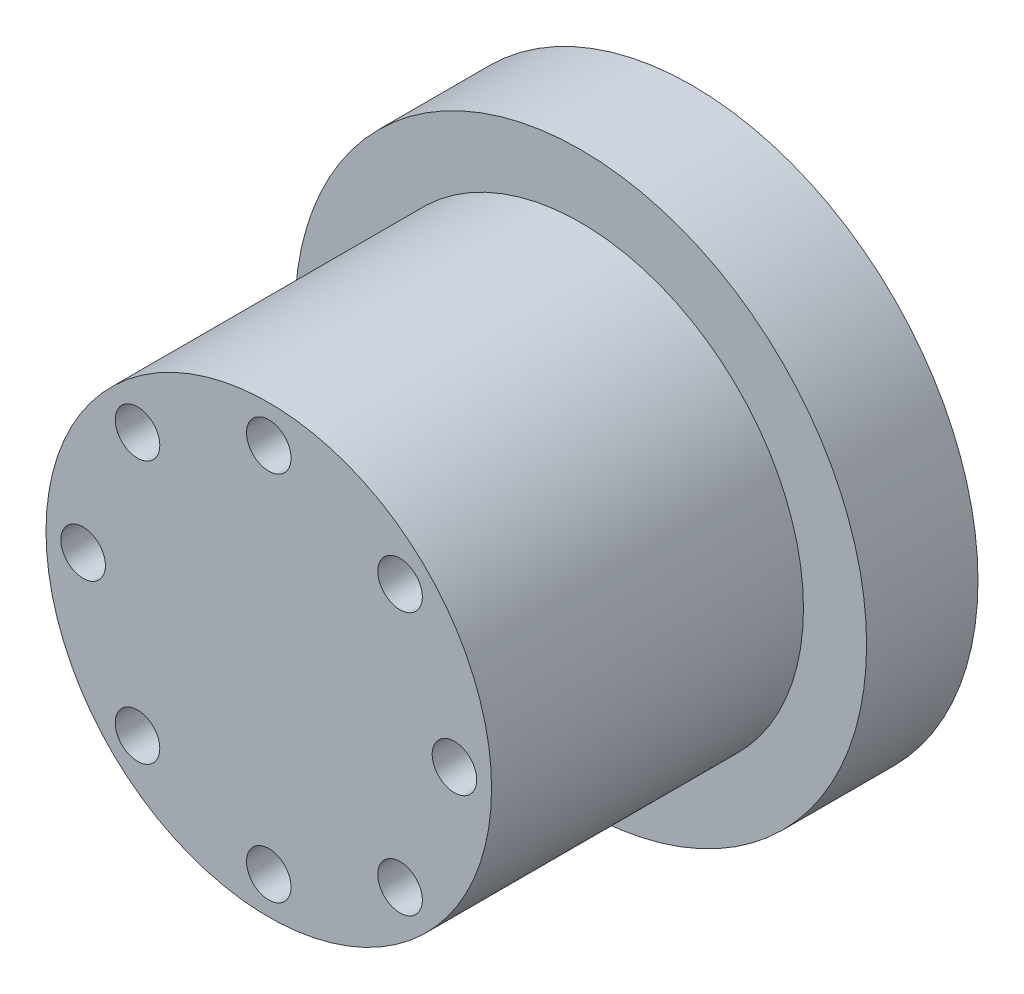
SolidWorks part; units mm, degrees
ref_plane "Front Plane" through (0, 0, 0) normal (0, 0, 1) x (1, 0, 0)
ref_plane "Top Plane" through (0, 0, 0) normal (0, 1, 0) x (1, 0, 0)
ref_plane "Right Plane" through (0, 0, 0) normal (1, 0, 0) x (0, 0, -1)
sketch "Sketch2" plane through (0, 0, 0) normal (0, 0, 1) x (1, 0, 0)
  circle A0 centre (0, 0) radius 30
  circle A3 centre (0, 0) radius 38.5
  dimension "D1" = 60
  dimension "D2" = 77
extrude "Boss-Extrude1" add sketch "Sketch2" along normal blind 42 contours A0
extrude "Boss-Extrude2" add sketch "Sketch2<4>" against normal blind 15 contours A0 | A0 region at (0, 0, 0) region at (-37.4111, 0, 0)
sketch "Sketch2<4>" plane through (0, 0, 0) normal (0, 0, 1) x (1, 0, 0) same geometry as "Sketch2"
sketch "Sketch3" plane through (0, 0, -15) normal (0, 0, -1) x (-1, 0, 0)
  circle A1 centre (0, 25) radius 3
  circle A2 centre (25, 0) radius 3
  circle A3 centre (0, -25) radius 3
  circle A4 centre (-25, 0) radius 3
  circle A5 centre (0, 0) radius 25 construction
  point P14 (0, 0)
  dimension "D1" = 4
  dimension "D2" = 6
  dimension "D3" = 50
extrude "Cut-Extrude1" cut sketch "Sketch3" against normal blind 10
sketch "Sketch4" plane through (0, 0, 42) normal (0, 0, 1) x (1, 0, 0)
  circle A1 centre (0, 25) radius 3
  circle A2 centre (17.6777, 17.6777) radius 3
  circle A3 centre (25, 0) radius 3
  circle A4 centre (17.6777, -17.6777) radius 3
  circle A5 centre (0, -25) radius 3
  circle A6 centre (-17.6777, -17.6777) radius 3
  circle A7 centre (-25, 0) radius 3
  circle A8 centre (-17.6777, 17.6777) radius 3
  circle A9 centre (0, 0) radius 25 construction
  point P21 (0, 0)
  dimension "D1" = 8
  dimension "D2" = 50
  dimension "D3" = 6
extrude "Cut-Extrude2" cut sketch "Sketch4" against normal blind 10
